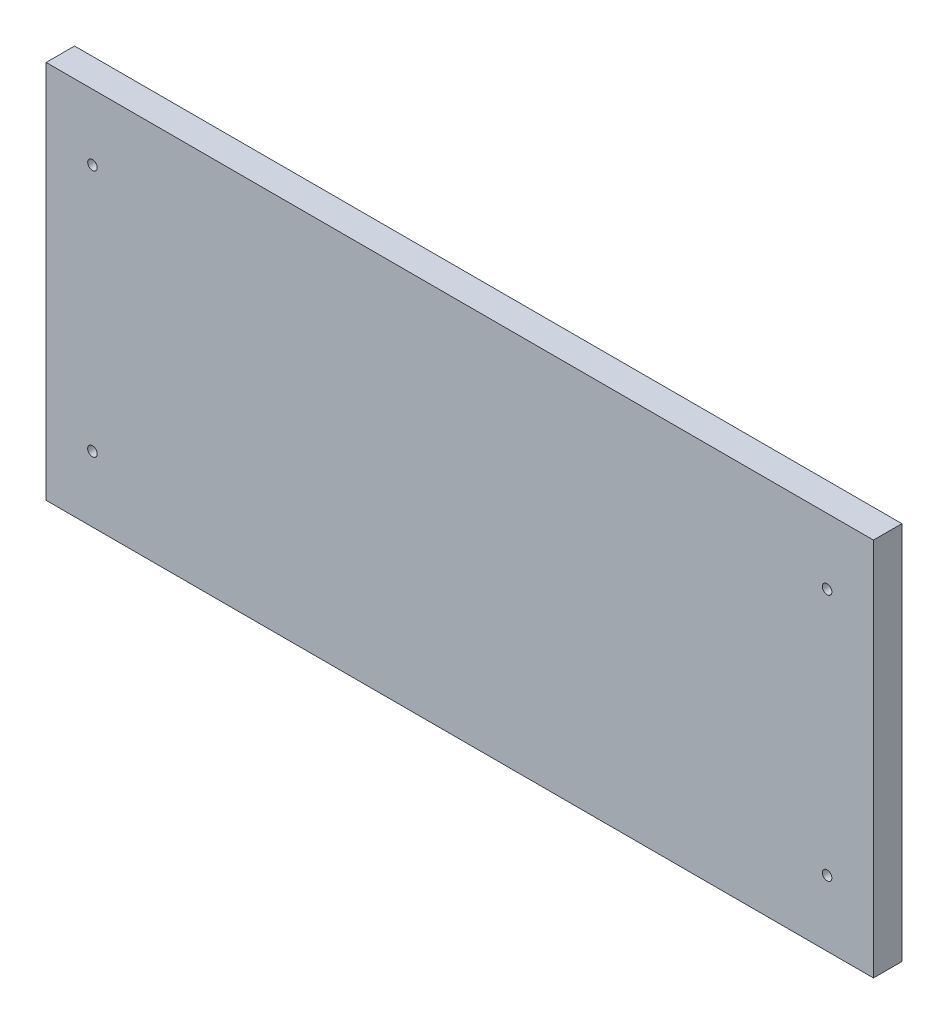
SolidWorks part; units mm, degrees
ref_plane "Front Plane" through (0, 0, 0) normal (0, 0, 1) x (1, 0, 0)
ref_plane "Top Plane" through (0, 0, 0) normal (0, 1, 0) x (1, 0, 0)
ref_plane "Right Plane" through (0, 0, 0) normal (1, 0, 0) x (0, 0, -1)
sketch "Sketch1" plane through (0, 0, 0) normal (0, 0, 1) x (1, 0, 0)
  line L1 (0, 0) -> (277.05, 0)
  line L2 (0, 0) -> (0, 127)
  line L3 (0, 127) -> (277.05, 127)
  line L4 (277.05, 0) -> (277.05, 127)
  line L5 (9.525, 127) -> (9.525, 0) construction
  line L7 (267.525, 127) -> (267.525, 0) construction
  circle A3 centre (15.525, 105) radius 1.6
  circle A4 centre (15.525, 22) radius 1.6
  circle A5 centre (261.525, 105) radius 1.6
  circle A6 centre (261.525, 22) radius 1.6
  dimension "D14" = 3.2
  dimension "D17" = 3.2
  dimension "D19" = 3.2
  dimension "D20" = 3.2
  dimension "D1" = 127
  dimension "D2" = 277.05
  dimension "D3" = 9.525
  dimension "D5" = 9.525
  dimension "D13" = 6
  dimension "D15" = 22
  dimension "D16" = 6
  dimension "D18" = 22
  dimension "D21" = 6
  dimension "D22" = 6
  dimension "D23" = 22
  dimension "D24" = 22
extrude "Wall" add sketch "Sketch1" along normal blind 9.525
sketch "Sketch2" plane through (0, 0, 9.525) normal (0, 0, 1) x (1, 0, 0)
  line L0 (277.05, 127) -> (0, 127) construction
  line L1 (0, 127) -> (0, 0) construction
  line L2 (95.53, 107.95) -> (138.525, 107.95) construction
  line L3 (181.52, 107.95) -> (138.525, 107.95) construction
  circle A0 centre (138.525, 107.95) radius 5.6295
  circle A1 centre (95.53, 107.95) radius 5.6295
  circle A2 centre (181.52, 107.95) radius 5.6295
  point P4 (138.525, 127)
  dimension "D1" = 11.259
  dimension "D2" = 19.05
  dimension "D3" = 95.53
extrude "RodCutouts" [suppressed] cut sketch "Sketch2" against normal up to next
sketch "Sketch3" [suppressed] plane through (0, 0, 9.525) normal (0, 0, 1) x (1, 0, 0)
  line L0 (277.05, 127) -> (0, 127) construction
  line L1 (50.8, 88.9) -> (226.25, 88.9)
  line L2 (50.8, 88.9) -> (50.8, 114.3)
  line L3 (50.8, 114.3) -> (226.25, 114.3)
  line L4 (226.25, 88.9) -> (226.25, 114.3)
  line L5 (50.8, 88.9) -> (226.25, 114.3) construction
  line L6 (50.8, 114.3) -> (226.25, 88.9) construction
  line L7 (0, 127) -> (0, 0) construction
  point P0 (138.525, 101.6)
  point P9 (138.525, 127)
  dimension "D1" = 25.4
  dimension "D2" = 50.8
  dimension "D3" = 25.4
extrude "CannulusLargeCutout" [suppressed] cut sketch "Sketch3" against normal up to next
sketch "Sketch4" [suppressed] plane through (0, 0, 9.525) normal (0, 0, 1) x (1, 0, 0)
  line L0 (15.525, 103.5) -> (261.525, 103.5) construction
  line L1 (15.525, 105) -> (15.525, 22) construction
  line L2 (261.525, 105) -> (261.525, 22) construction
  circle A0 centre (38.525, 103.5) radius 9
  circle A1 centre (38.525, 63.5) radius 9
  circle A2 centre (88.525, 63.5) radius 9
  circle A3 centre (138.525, 63.5) radius 9
  circle A4 centre (88.525, 103.5) radius 9
  circle A5 centre (138.525, 103.5) radius 9
  circle A6 centre (188.525, 103.5) radius 9
  circle A7 centre (238.525, 103.5) radius 9
  circle A8 centre (188.525, 63.5) radius 9
  circle A9 centre (238.525, 63.5) radius 9
  circle A10 centre (38.525, 23.5) radius 9
  circle A11 centre (88.525, 23.5) radius 9
  circle A12 centre (138.525, 23.5) radius 9
  circle A13 centre (188.525, 23.5) radius 9
  circle A14 centre (238.525, 23.5) radius 9
  point P9 (15.525, 63.5)
  point P23 (138.525, 103.5)
  dimension "D1" = 18
  dimension "D2" = 5
  dimension "D4" = 3
extrude "CannulusHoles" [suppressed] cut sketch "Sketch4" against normal up to next
equation "\"Length\"= 283mm"
equation "\"Width\"= 225mm"
equation "\"WallThickness\"= 12.5mm"
equation "\"UpperWaterJacketThickness\"= 28mm"
equation "\"SpacerHeight\"= 80.2mm"
equation "\"SpacerCornerWidth\"= 10mm"
equation "\"SpacerCornerHeight\"= 60.16mm"
equation "\"SpacerPegDiameter\"= 10mm"
equation "\"SpacerPegHeight\"= 10mm"
equation "\"TubingShort\"= 110mm"
equation "\"TubingLong\"= 175mm"
equation "\"PlateLength\"= 252mm"
equation "\"PlateWidth\"= 190mm"
equation "\"PlateHoleDiameter\"= 5.9mm"
equation "\"PlateHoleBottom\"= 2mm"
equation "\"PlateHoleSide\"= 1.55mm"
equation "\"PlateHoleSpacing\"= 3.1mm"
equation "\"PlateThickness\"= 1.55mm"
equation "\"ReservoirBottom\"= 12.5mm"
equation "\"ReservoirSupportWidth\"= 12mm"
equation "\"ReservoirSupportHeight\"= 15.1mm"
equation "\"ReservoirSupportPlacementHeight\"= 50mm"
equation "\"ReservoirHoleDiameter\"= 12.7mm"
equation "\"ReservoirHoleRight\"= 25mm"
equation "\"ReservoirHoleTop\"= \"ReservoirSupportPlacementHeight\""
equation "\"ReservoirHeight\"= 90mm"
equation "\"ReservoirPortBottom\"= 4mm"
equation "\"ReservoirPortTop\"= 10mm"
equation "\"ReservoirPortWidth\"= 101mm"
equation "\"CustomSpacerWallThickness\"= 0.375in"
equation "\"CustomSpacerHeight\"= 5in"
equation "\"CustomSpacerRodHoleHeight\"= .75in"
equation "\"CustomSpacerRodHoleDiameter\"= .3125in"
equation "\"ScrewBlockSide\"= 12mm"
equation "\"ScrewBlockUpperHeight\"= 16mm"
equation "\"ScrewBlockLowerHeight\"= 16mm"
equation "\"InternalLength\"= \"Length\" - ( 2 * \"WallThickness\" )"
equation "\"InternalWidth\"= \"Width\" - ( 2 * \"WallThickness\" )"
equation "\"CustomSpacerPegHeight\"= 1in"
equation "\"CustomSpacerScrewBore\"=3.2mm"
equation "\"CustomSpacerScrewDepth\"=10mm"
equation "\"D1@Sketch1\"=\"CustomSpacerHeight\""
equation "\"D2@Sketch1\"=\"InternalLength\"+\"CustomSpacerWallThickness\"*2"
equation "\"D3@Sketch1\"=\"CustomSpacerWallThickness\""
equation "\"D5@Sketch1\"=\"CustomSpacerWallThickness\""
equation "\"D1@Wall\" = \"CustomSpacerWallThickness\""
equation "\"D13@Sketch1\"=\"ScrewBlockSide\"/2"
equation "\"D14@Sketch1\"=\"CustomSpacerScrewBore\""
equation "\"D15@Sketch1\"=\"ScrewBlockUpperHeight\"+\"ScrewBlockSide\"/2"
equation "\"D16@Sketch1\"=\"ScrewBlockSide\"/2"
equation "\"D17@Sketch1\"=\"CustomSpacerScrewBore\""
equation "\"D18@Sketch1\"=\"ScrewBlockLowerHeight\"+\"ScrewBlockSide\"/2"
equation "\"D19@Sketch1\"=\"CustomSpacerScrewBore\""
equation "\"D20@Sketch1\"=\"CustomSpacerScrewBore\""
equation "\"D21@Sketch1\"=\"ScrewBlockSide\"/2"
equation "\"D22@Sketch1\"=\"ScrewBlockSide\"/2"
equation "\"D23@Sketch1\"=\"ScrewBlockLowerHeight\"+\"ScrewBlockSide\"/2"
equation "\"D24@Sketch1\"=\"ScrewBlockUpperHeight\"+\"ScrewBlockSide\"/2"
equation "\"RodCutout\"=7.94"
equation "\"D1@Sketch2\"=\"RodCutout\""
equation "\"D3@Sketch2\"=86mm+9.53mm"
equation "\"CannulusTubingDiameter\"=15"
equation "\"D1@Sketch4\"=\"CannulusTubingDiameter\" * 1.2"
